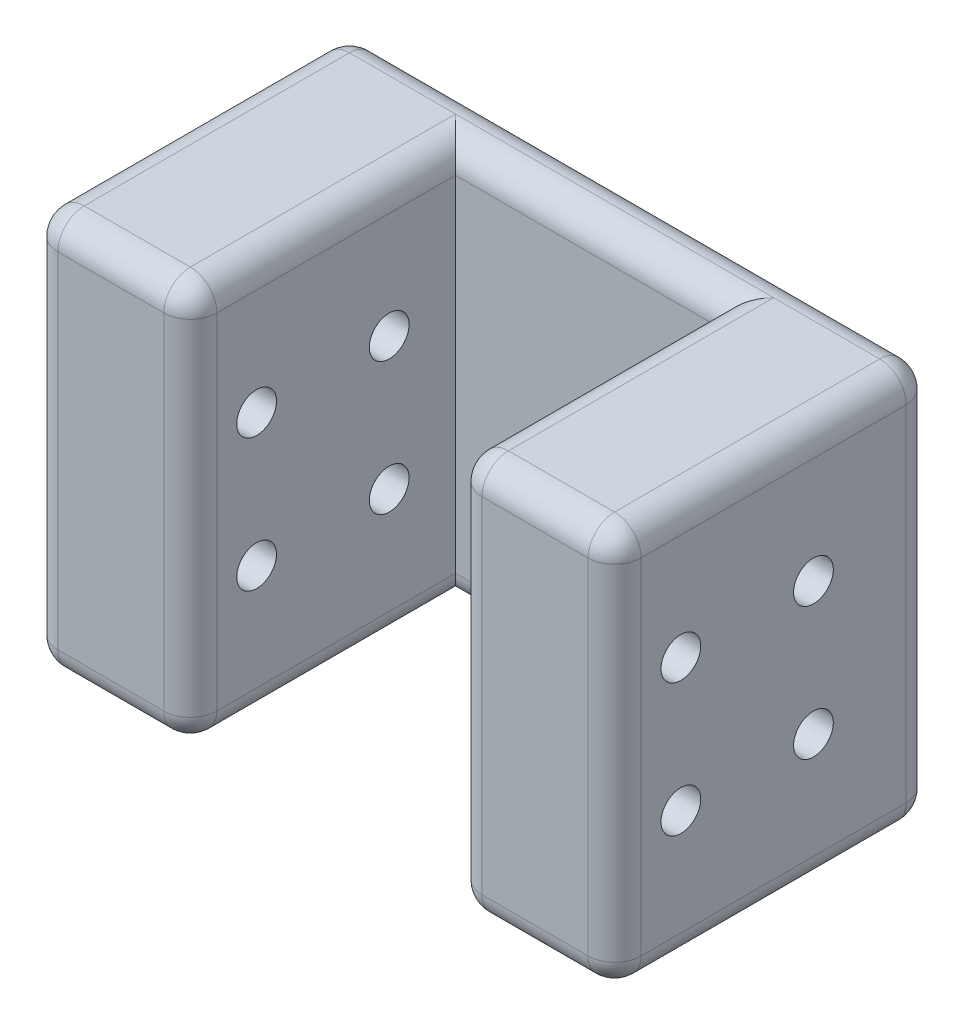
SolidWorks part; units mm, degrees
ref_plane "前视基准面" through (0, 0, 0) normal (0, 0, 1) x (1, 0, 0)
ref_plane "上视基准面" through (0, 0, 0) normal (0, 1, 0) x (1, 0, 0)
ref_plane "右视基准面" through (0, 0, 0) normal (1, 0, 0) x (0, 0, -1)
sketch "草图1" plane through (0, 0, 0) normal (0, 0, 1) x (1, 0, 0)
  line L1 (-22, -15) -> (22, -15)
  line L2 (-22, -15) -> (-22, 15)
  line L3 (-22, 15) -> (22, 15)
  line L4 (22, -15) -> (22, 15)
  line L5 (-22, -15) -> (22, 15) construction
  line L6 (-22, 15) -> (22, -15) construction
  point P0 (0, 0)
  dimension "D1" = 30
  dimension "D2" = 44
extrude "凸台-拉伸1" add sketch "草图1" along normal blind 24
sketch "草图5" plane through (0, 0, 24) normal (0, 0, 1) x (1, 0, 0)
  line L0 (22, -15) -> (22, 15) construction
  line L1 (-10, -16.4155) -> (10, -16.4155)
  line L2 (-10, -16.4155) -> (-10, 17.6553)
  line L3 (-10, 17.6553) -> (10, 17.6553)
  line L4 (10, -16.4155) -> (10, 17.6553)
  line L5 (-22, 15) -> (-22, -15) construction
  dimension "D1" = 12
  dimension "D2" = 12
extrude "切除-拉伸3" cut sketch "草图5" against normal blind 20
sketch "草图6" plane through (22, 0, 0) normal (1, 0, 0) x (0, 0, -1)
  line L0 (-24, -15) -> (-24, 15) construction
  line L1 (-24, 15) -> (0, 15) construction
  circle A0 centre (-19, 5) radius 1.5
  circle A1 centre (-19, -5) radius 1.5
  circle A2 centre (-9, -5) radius 1.5
  circle A3 centre (-9, 5) radius 1.5
  dimension "D1" = 3
  dimension "D2" = 3
  dimension "D3" = 3
  dimension "D4" = 3
  dimension "D5" = 5
  dimension "D6" = 10
  dimension "D7" = 10
  dimension "D8" = 10
extrude "切除-拉伸4" cut sketch "草图6" against normal blind 44
fillet "圆角1" radius 2 16 edges at (-22, 15, 12) (0, 15, 0) (22, 15, 12) (16, 15, 24) (10, 15, 14) (0, 15, 4) (-10, 15, 14) (-16, 15, 24) (16, -15, 24) (0, -15, 0) (22, -15, 12) (10, -15, 14) (0, -15, 4) (-16, -15, 24) (-22, -15, 12) (-10, -15, 14)
fillet "圆角2" radius 2 18 edges at (10.5858, 14.4142, 23.4142) (10.5858, -14.4142, 23.4142) (21.4142, -14.4142, 23.4142) (21.4142, 14.4142, 23.4142) (-21.4142, 14.4142, 23.4142) (-21.4142, -14.4142, 23.4142) (-10.5858, -14.4142, 23.4142) (-10.5858, 14.4142, 23.4142) (-21.4142, 14.4142, 0.5858) (-21.4142, -14.4142, 0.5858) (21.4142, -14.4142, 0.5858) (21.4142, 14.4142, 0.5858) (10, 0, 24) (22, 0, 24) (-22, 0, 24) (-10, 0, 24) (-22, 0, 0) (22, 0, 0)
